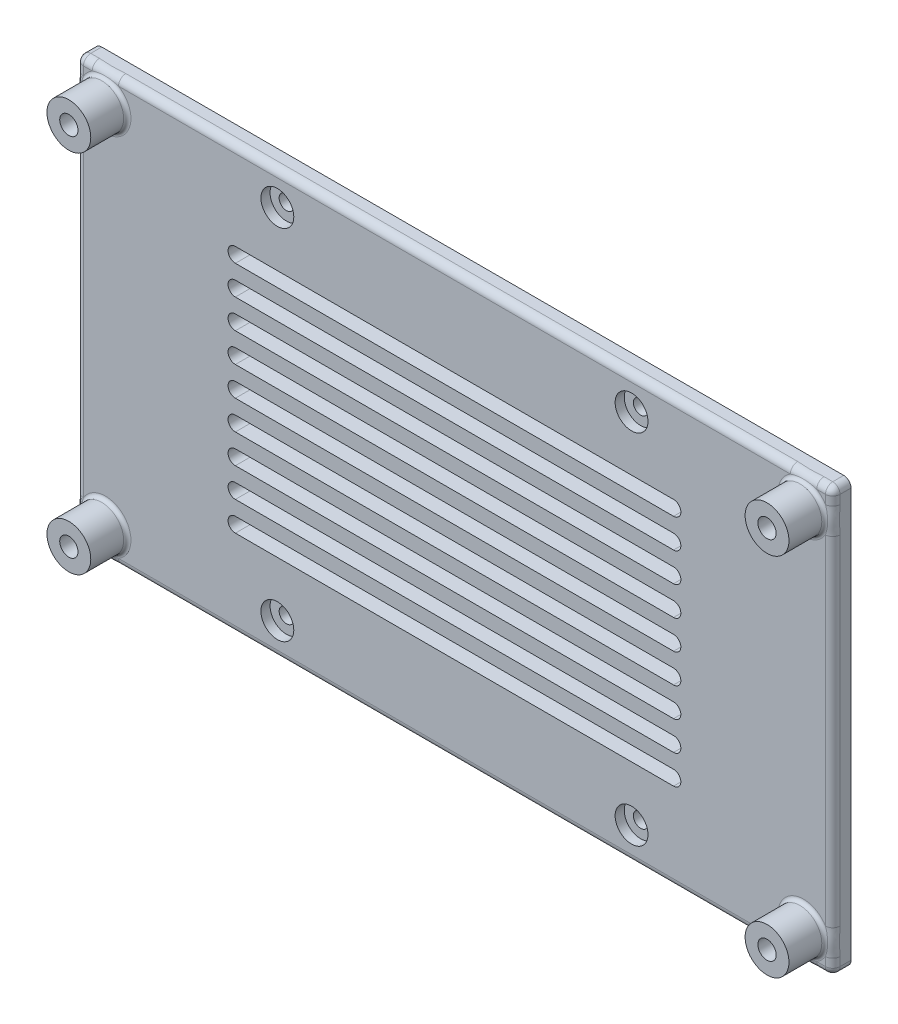
SolidWorks part; units mm, degrees
ref_plane "Plan de face" through (0, 0, 0) normal (0, 0, 1) x (1, 0, 0)
ref_plane "Plan de dessus" through (0, 0, 0) normal (0, 1, 0) x (1, 0, 0)
ref_plane "Plan de droite" through (0, 0, 0) normal (1, 0, 0) x (0, 0, -1)
sketch "Esquisse1" plane through (0, 0, 0) normal (0, 0, 1) x (1, 0, 0)
  line L1 (-51.8, 29) -> (51.8, 29)
  line L2 (-51.8, 29) -> (-51.8, -29)
  line L3 (-51.8, -29) -> (51.8, -29)
  line L4 (51.8, 29) -> (51.8, -29)
  line L5 (-51.8, 29) -> (51.8, -29) construction
  line L6 (-51.8, -29) -> (51.8, 29) construction
  line L7 (24.25, -24.5) -> (-24.25, -24.5) construction
  line L8 (24.25, -24.5) -> (24.25, 24.5) construction
  line L9 (24.25, 24.5) -> (-24.25, 24.5) construction
  line L10 (-24.25, -24.5) -> (-24.25, 24.5) construction
  line L11 (24.25, -24.5) -> (-24.25, 24.5) construction
  line L12 (24.25, 24.5) -> (-24.25, -24.5) construction
  circle A0 centre (-24.25, -24.5) radius 1.005
  circle A1 centre (-24.25, 24.5) radius 1.005
  circle A2 centre (24.25, -24.5) radius 1.005
  circle A3 centre (24.25, 24.5) radius 1.005
  point P0 (0, 0)
  point P5 (0, 0)
  point P13 (0, 0)
  dimension "D5" = 2.01
  dimension "D6" = 2.01
  dimension "D7" = 2.01
  dimension "D8" = 2.01
  dimension "D1" = 58
  dimension "D2" = 103.6
  dimension "D3" = 48.5
  dimension "D4" = 49
extrude "Boss.-Extru.1" add sketch "Esquisse1" along normal blind 2.5
sketch "Esquisse3" plane through (0, 0, 2.5) normal (0, 0, 1) x (1, 0, 0)
  line L0 (51.8, 29) -> (-51.8, 29) construction
  line L1 (-51.8, 29) -> (-51.8, -29) construction
  line L2 (-51.8, -29) -> (51.8, -29) construction
  line L3 (51.8, -29) -> (51.8, 29) construction
  circle A0 centre (-47.8, 25) radius 3
  circle A1 centre (47.8, 25) radius 3
  circle A2 centre (-47.8, -25) radius 3
  circle A3 centre (47.8, -25) radius 3
  point P17 (-47.8, 25)
  point P18 (-47.8, -25)
  point P19 (47.8, -25)
  point P20 (47.8, 25)
  point P21 (0, 0)
  dimension "D3" = 4
  dimension "D1" = 4
  dimension "D2" = 4
  dimension "D4" = 4
  dimension "D5" = 4
  dimension "D6" = 4
  dimension "D7" = 4
  dimension "D8" = 4
extrude "Boss.-Extru.2" add sketch "Esquisse3" along normal blind 5 contours A1 | A3 | A2 | A0
fillet "Congé2" radius 0.5 4 edges at (50.8, 25, 2.5) (50.8, -25, 2.5) (-44.8, -25, 2.5) (-44.8, 25, 2.5)
hole_wizard "Trou pour taraudage pour trou taraudé M32" positions "Esquisse15" profile "Esquisse16" hole size "M3" standard "AS"
sketch "Esquisse15" plane through (0, 0, 7.5) normal (0, 0, 1) x (1, 0, 0)
  point P0 (-47.8, -25)
  point P3 (47.8, -25)
  point P6 (47.8, 25)
  point P9 (-47.8, 25)
sketch "Esquisse16" plane through (-47.8, -25, 7.5) normal (1, 0, 0) x (0, -1, 0)
  line L0 (0, 0) -> (0, 5.7511)
  line L1 (0, 5.7511) -> (1.25, 5)
  line L2 (1.25, 5) -> (1.25, 0)
  line L5 (1.25, 0) -> (0, 0)
  line L10 (0, 5.7511) -> (-1.25, 5) construction
  line L11 (0, -6.35) -> (0, 107.95) construction
  dimension "Diamètre du perçage" = 2.5
  dimension "Profondeur du perçage" = 5
  dimension "Angle de pointe" = 118
sketch "Esquisse19" plane through (0, 0, 2.5) normal (0, 0, 1) x (1, 0, 0)
  circle A0 centre (24.25, -24.5) radius 2.25
  circle A1 centre (-24.25, -24.5) radius 2.25
  circle A2 centre (-24.25, 24.5) radius 2.25
  circle A3 centre (24.25, 24.5) radius 2.25
  point P12 (0, 0)
extrude "Enlèv. mat.-Extru.1" cut sketch "Esquisse19" against normal blind 1.25 contours A1 | A2 | A3 | A0
fillet "Congé3" radius 1 8 edges at (-51.8, 0, 2.5) (0, -29, 2.5) (0, 29, 2.5) (51.8, 0, 2.5) (51.8, -29, 1.25) (51.8, 29, 1.25) (-51.8, 29, 1.25) (-51.8, -29, 1.25)
sketch "Esquisse22" plane through (0, 0, 2.5) normal (0, 0, 1) x (1, 0, 0)
  line L0 (30, 0) -> (-30, 0) construction
  line L1 (30, -1) -> (-30, -1)
  line L2 (30, 1) -> (-30, 1)
  arc A0 (30, -1) -> (30, 1) centre (30, 0) ccw
  arc A1 (-30, 1) -> (-30, -1) centre (-30, 0) ccw
  point P2 (0, 0)
extrude "Enlèv. mat.-Extru.3" cut sketch "Esquisse22" against normal through all
pattern_linear "Répétition linéaire2" count 5 spacing 4 along (0, 1, 0) count 5 spacing 4 along (0, -1, 0) of "Enlèv. mat.-Extru.3" pattern seed only yes
